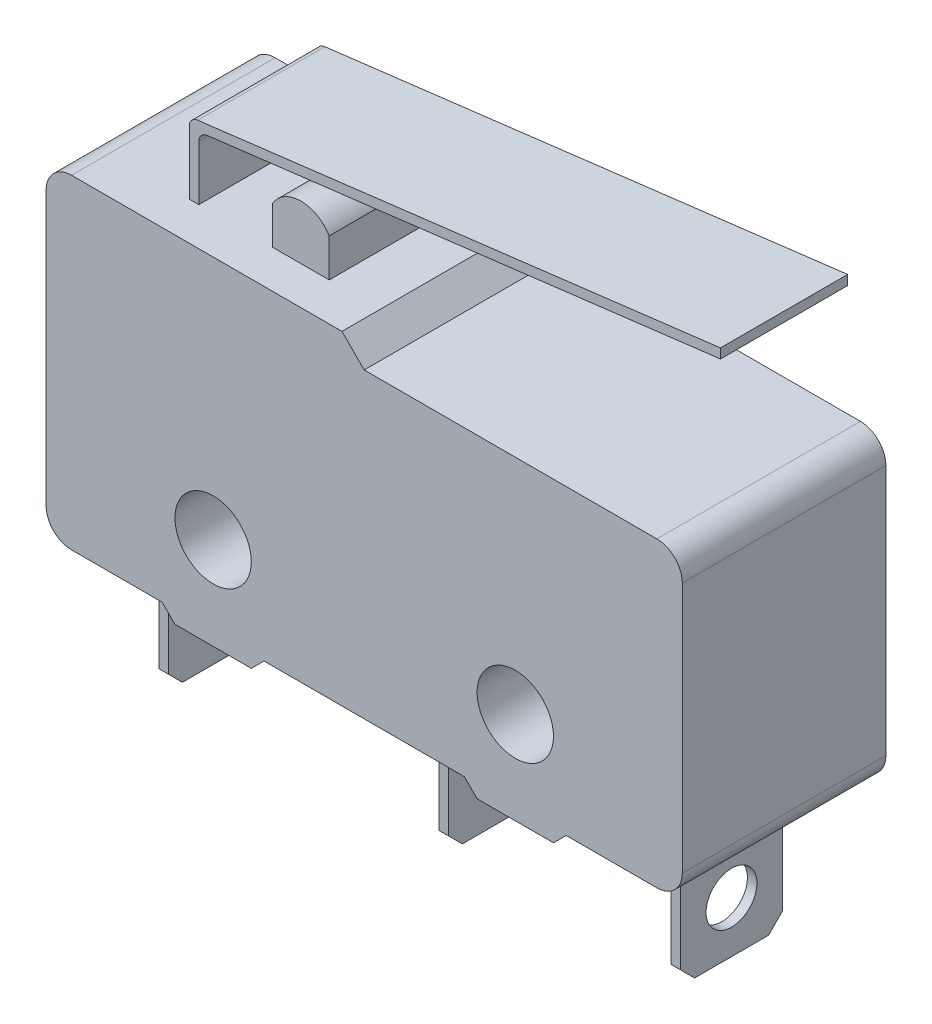
SolidWorks part; units mm, degrees
ref_plane "Front Plane" through (0, 0, 0) normal (0, 0, 1) x (1, 0, 0)
ref_plane "Top Plane" through (0, 0, 0) normal (0, 1, 0) x (1, 0, 0)
ref_plane "Right Plane" through (0, 0, 0) normal (1, 0, 0) x (0, 0, -1)
sketch "Sketch1" plane through (0, 0, 0) normal (0, 0, 1) x (1, 0, 0)
  line L1 (-10, 5.1) -> (10, 5.1)
  line L2 (-10, 5.1) -> (-10, -5.1)
  line L3 (-10, -5.1) -> (10, -5.1)
  line L4 (10, 5.1) -> (10, -5.1)
  line L5 (-10, 5.1) -> (10, -5.1) construction
  line L6 (-10, -5.1) -> (10, 5.1) construction
  point P0 (0, 0)
  dimension "D1" = 20
  dimension "D2" = 10.2
extrude "Boss-Extrude1" add sketch "Sketch1" along normal blind 6.4
sketch "Sketch2" plane through (0, -5.1, 0) normal (0, -1, 0) x (1, 0, 0)
  line L0 (-10, 6.4) -> (10, 6.4) construction
  line L1 (-8.0527, 4.8) -> (-7.7527, 4.8)
  line L2 (-8.0527, 4.8) -> (-8.0527, 1.6)
  line L3 (-8.0527, 1.6) -> (-7.7527, 1.6)
  line L4 (-7.7527, 4.8) -> (-7.7527, 1.6)
  line L5 (-8.0527, 4.8) -> (-7.7527, 1.6) construction
  line L6 (-8.0527, 1.6) -> (-7.7527, 4.8) construction
  point P0 (-7.9027, 3.2)
  dimension "D1" = 3.2
  dimension "D2" = 0.3
  dimension "D3" = 1.6
extrude "Boss-Extrude2" add sketch "Sketch2" along normal blind 3.9
sketch "Sketch3" plane through (-8.0527, 0, 0) normal (-1, 0, 0) x (0, 0, 1)
  line L0 (4.3622, -9) -> (4.8, -8.5622)
  line L1 (4.8, -9) -> (1.6, -9) construction
  line L2 (4.8, -9) -> (4.8, -5.1) construction
  line L3 (2.0378, -9) -> (1.6, -8.5622)
  line L4 (1.6, -9) -> (1.6, -5.1) construction
  line L5 (4.8, -9) -> (4.3622, -9)
  line L6 (4.8, -9) -> (4.8, -8.5622)
  line L7 (2.0378, -9) -> (1.6, -9)
  line L8 (1.6, -9) -> (1.6, -8.5622)
  circle A0 centre (3.2, -7.3954) radius 0.8
  dimension "D1" = 1.6
  dimension "D2" = 1.6
extrude "Cut-Extrude1" cut sketch "Sketch3" against normal up to next
pattern_linear "LPattern1" count 2 spacing 8.8 along (1, 0, 0) of "Boss-Extrude2", "Cut-Extrude1"
pattern_linear "LPattern2" count 2 spacing 16.1 along (1, 0, 0) of "Boss-Extrude2", "Cut-Extrude1"
sketch "Sketch4" plane through (0, 5.1, 0) normal (0, 1, 0) x (1, 0, 0)
  line L1 (10, -6.4) -> (-10, -6.4) construction
  line L2 (10, 0) -> (0, 0)
  line L3 (10, 0) -> (10, -6.4)
  line L4 (10, -6.4) -> (0, -6.4)
  line L5 (0, 0) -> (0, -6.4)
extrude "Cut-Extrude2" cut sketch "Sketch4" against normal blind 0.7
sketch "Sketch5" plane through (0, 0, 6.4) normal (0, 0, 1) x (1, 0, 0)
  line L0 (-10, -5.1) -> (10, -5.1) construction
  line L1 (-10, 5.1) -> (-10, -5.1) construction
  circle A0 centre (-4.75, -2.6) radius 1.2
  circle A1 centre (4.75, -2.6) radius 1.2
  dimension "D1" = 2.4
  dimension "D2" = 2.5
  dimension "D3" = 9.5
  dimension "D4" = 5.25
extrude "Cut-Extrude3" cut sketch "Sketch5" against normal through all
sketch "Sketch7" plane through (0, 0, 6.4) normal (0, 0, 1) x (1, 0, 0)
  line L1 (-3.55, -5.5) -> (-5.95, -5.5)
  line L4 (5.95, -5.5) -> (3.55, -5.5)
  line L6 (-4.75, -5.1) -> (-4.75, -8.7492) construction
  line L7 (4.75, -5.1) -> (4.75, -8.7492) construction
  line L8 (-10, -5.1) -> (10, -5.1) construction
  line L9 (-5.95, -5.5) -> (-6.35, -5.1)
  line L10 (-3.55, -5.5) -> (-3.15, -5.1)
  line L11 (-3.15, -5.1) -> (-6.35, -5.1)
  line L12 (3.55, -5.5) -> (3.15, -5.1)
  line L13 (5.95, -5.5) -> (6.35, -5.1)
  line L14 (6.35, -5.1) -> (3.15, -5.1)
  dimension "D1" = 0.4
extrude "Boss-Extrude3" add sketch "Sketch7" against normal up to surface (6.4 mm away) up to face at (5.95, -2.6, 0)
chamfer "Chamfer1" distance 0.7 angle 45 1 edges at (0, 5.1, 3.2)
fillet "Fillet1" radius 0.8 4 edges at (10, -5.1, 3.2) (10, 4.4, 3.2) (-10, -5.1, 3.2) (-10, 5.1, 3.2)
sketch "Sketch8" plane through (0, 0, 6.4) normal (0, 0, 1) x (1, 0, 0)
  line L0 (-2.3004, 5.1) -> (-2.3004, 6.3)
  line L1 (-0.7, 5.1) -> (-9.2, 5.1) construction
  line L3 (-4.0766, 6.3) -> (-4.0766, 5.1)
  line L17 (6.35, -5.1) -> (9.2, -5.1)
  line L18 (10, -4.3) -> (10, 3.6)
  line L19 (9.2, 4.4) -> (0, 4.4)
  line L20 (0, 4.4) -> (-0.7, 5.1)
  line L21 (-0.7, 5.1) -> (-9.2, 5.1)
  line L22 (-10, 4.3) -> (-10, -4.3)
  line L23 (-9.2, -5.1) -> (-6.35, -5.1)
  line L24 (-6.35, -5.1) -> (-5.95, -5.5)
  line L25 (-5.95, -5.5) -> (-3.55, -5.5)
  line L26 (-3.55, -5.5) -> (-3.15, -5.1)
  line L27 (-3.15, -5.1) -> (3.15, -5.1)
  line L28 (3.15, -5.1) -> (3.55, -5.5)
  line L29 (3.55, -5.5) -> (5.95, -5.5)
  line L30 (5.95, -5.5) -> (6.35, -5.1)
  line L35 (-2.3004, 5.1) -> (-4.0766, 5.1)
  arc A0 (-2.3004, 6.3) -> (-4.0766, 6.3) centre (-3.1885, 5.7672) ccw
  arc A5 (9.2, -5.1) -> (10, -4.3) centre (9.2, -4.3) ccw
  arc A6 (10, 3.6) -> (9.2, 4.4) centre (9.2, 3.6) ccw
  arc A7 (-9.2, 5.1) -> (-10, 4.3) centre (-9.2, 4.3) ccw
  arc A8 (-10, -4.3) -> (-9.2, -5.1) centre (-9.2, -4.3) ccw
  dimension "D1" = 1.2
  dimension "D2" = 0
extrude "Boss-Extrude4" add sketch "Sketch8" against normal blind 4 from offset 1.2 offset against normal yes
ref_plane "Plane3" through (0, 0, 5.2) normal (0, 0, 1) x (1, 0, 0)
sketch "Sketch11" plane through (0, 0, 5.2) normal (0, 0, 1) x (1, 0, 0)
  line L0 (-0.7, 5.1) -> (-9.2, 5.1) construction
  line L1 (-6.4, 5.1) -> (-6.7, 5.1)
  line L2 (-6.7, 5.1) -> (-6.7, 7.3495)
  line L3 (-6.7, 7.3495) -> (10, 9.4)
  line L4 (0, 4.4) -> (9.2, 4.4) construction
  line L5 (10, -4.3) -> (10, 3.6) construction
  line L6 (10, 9.0977) -> (10, 9.4)
  line L7 (-6.4, 5.1) -> (-6.4, 7.0841)
  line L8 (-6.4, 7.0841) -> (10, 9.0977)
  line L9 (-6.4, 7.0841) -> (10.0366, 9.1022) construction
  circle A0 centre (4.75, -2.6) radius 1.2 construction
  dimension "D1" = 7
  dimension "D2" = 16.7
  dimension "D3" = 12
  dimension "D4" = 0.3
extrude "Boss-Extrude5" add sketch "Sketch11" against normal up to surface (4 mm away) up to face at (-3.1885, 5.8257, 1.2)
fillet "Fillet2" radius 0.3 2 edges at (-6.4, 7.0841, 3.2) (-6.7, 7.3495, 3.2)
